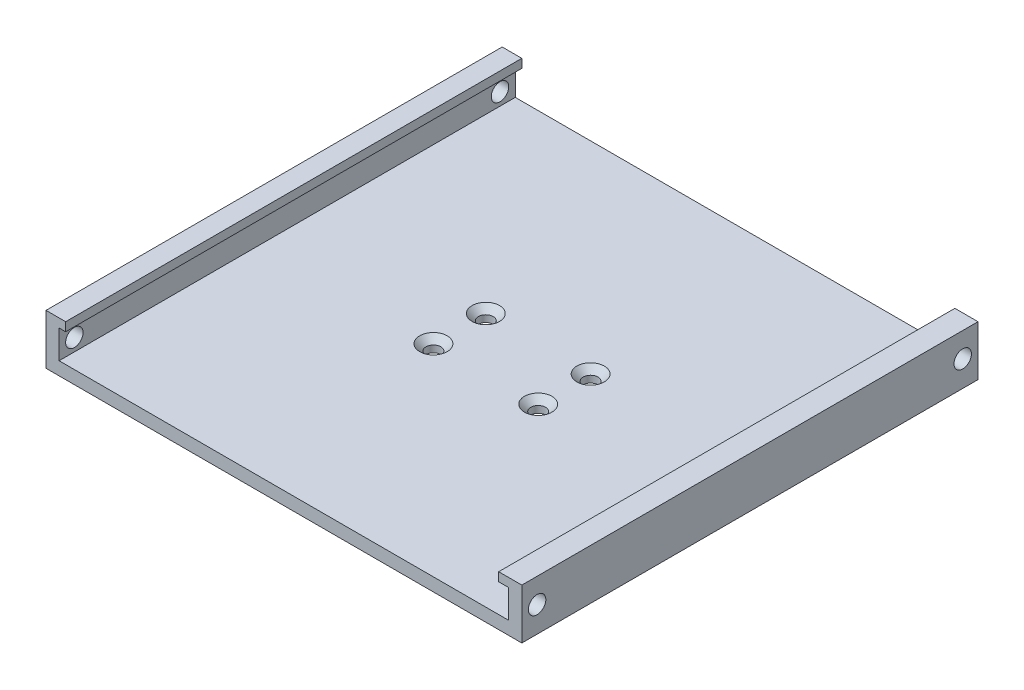
SolidWorks part; units mm, degrees
material "PET"
ref_plane "Front Plane" through (0, 0, 0) normal (0, 0, 1) x (1, 0, 0)
ref_plane "Top Plane" through (0, 0, 0) normal (0, 1, 0) x (1, 0, 0)
ref_plane "Right Plane" through (0, 0, 0) normal (1, 0, 0) x (0, 0, -1)
sketch "Sketch1" plane through (0, 0, 0) normal (0, 0, 1) x (1, 0, 0)
  line L0 (-50, 11.5) -> (-50, 9.5)
  line L1 (-54.5, 11.5) -> (-50, 11.5)
  line L2 (-54.5, 11.5) -> (-54.5, 0)
  line L3 (-54.5, 0) -> (54.5, 0)
  line L4 (54.5, 11.5) -> (54.5, 0)
  line L5 (-51.5, 9.5) -> (-50, 9.5)
  line L6 (-51.5, 9.5) -> (-51.5, 3)
  line L7 (-51.5, 3) -> (51.5, 3)
  line L8 (51.5, 9.5) -> (51.5, 3)
  line L9 (49.2, 11.5) -> (49.2, 9.5)
  line L10 (49.2, 11.5) -> (54.5, 11.5)
  line L11 (49.2, 9.5) -> (51.5, 9.5)
  point P4 (0, 3)
  dimension "D1" = 109
  dimension "D2" = 3
  dimension "D3" = 4.5
  dimension "D4" = 5.3
  dimension "D5" = 3
  dimension "D6" = 6.5
  dimension "D7" = 2
extrude "Boss-Extrude1" add sketch "Sketch1" along normal blind 52.25 and the other way blind 52.25
sketch "Sketch2" plane through (-54.5, 0, 0) normal (-1, 0, 0) x (0, 0, 1)
  line L1 (-52.25, 11.5) -> (-40.25, 11.5)
  line L2 (-52.25, 11.5) -> (-52.25, 0)
  line L3 (-52.25, 0) -> (-49.25, 0)
  line L4 (-40.25, 11.5) -> (-40.25, 9.5)
  line L5 (-52.25, 0) -> (52.25, 0) construction
  line L8 (-40.25, 9.5) -> (-49.25, 9.5)
  line L9 (-49.25, 0) -> (-49.25, 9.5)
  dimension "D1" = 12
  dimension "D2" = 9.5
  dimension "D3" = 3
sketch "Sketch3" plane through (0, 3, 0) normal (0, 1, 0) x (1, 0, 0)
  line L1 (-12, 6) -> (12, 6) construction
  line L2 (-12, 6) -> (-12, -6) construction
  line L3 (-12, -6) -> (12, -6) construction
  line L4 (12, 6) -> (12, -6) construction
  point P4 (12, 0)
  point P6 (0, -6)
  dimension "D1" = 12
  dimension "D2" = 24
hole_wizard "CSK for M3 Flat Head Machine Screw1" positions "3DSketch1" profile "Sketch4" countersink size "M3" standard "ANSI Metric" end condition through all
sketch3d "3DSketch1"
  point P0 (-12, 3, -6)
  point P3 (-12, 3, 6)
  point P6 (12, 3, 6)
  point P9 (12, 3, -6)
sketch "Sketch4" plane through (-12, 3, -6) normal (1, 0, 0) x (0, 0, 1)
  line L0 (0, 0) -> (0, 3)
  line L1 (0, 3) -> (1.7, 3)
  line L2 (1.7, 3) -> (1.7, 1.45)
  line L3 (1.7, 1.45) -> (3.15, 0)
  line L5 (3.15, 0) -> (0, 0)
  line L6 (-1.7, 1.45) -> (-3.15, 0) construction
  line L11 (0, -6.35) -> (0, 107.95) construction
  dimension "Thru Hole Dia." = 3.4
  dimension "Thru Hole Depth" = 3
  dimension "Near C'Sink Dia." = 6.3
  dimension "Near C'Sink Angle" = 90
sketch "Sketch5" plane through (54.5, 0, 0) normal (1, 0, 0) x (0, 0, -1)
  circle A1 centre (-48.75, 5.875) radius 2 construction
  circle A2 centre (-48.75, 5.875) radius 2
  circle A3 centre (48.75, 5.875) radius 2 construction
  circle A4 centre (48.75, 5.875) radius 2
extrude "Cut-Extrude1" cut sketch "Sketch5" against normal through all
